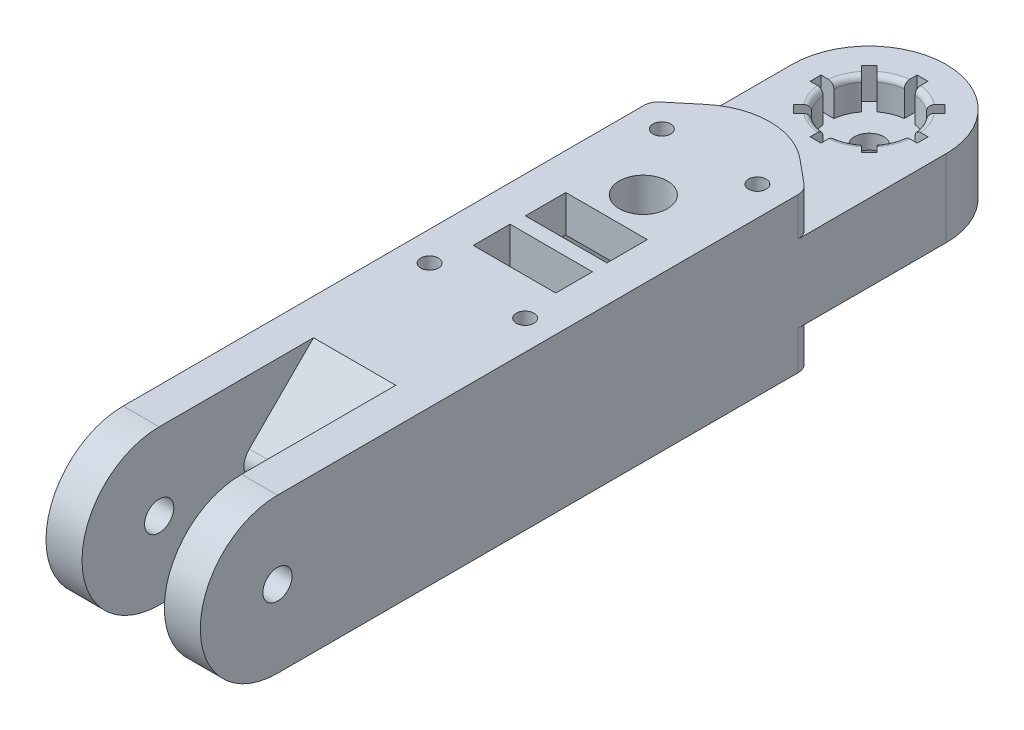
SolidWorks part; units mm, degrees
ref_plane "Front Plane" through (0, 0, 0) normal (0, 0, 1) x (1, 0, 0)
ref_plane "Top Plane" through (0, 0, 0) normal (0, 1, 0) x (1, 0, 0)
ref_plane "Right Plane" through (0, 0, 0) normal (1, 0, 0) x (0, 0, -1)
sketch "Sketch1" plane through (0, 0, 0) normal (0, 0, 1) x (1, 0, 0)
  line L1 (-21, 21) -> (21, 21)
  line L2 (-21, 21) -> (-21, -21)
  line L3 (-21, -21) -> (21, -21)
  line L4 (21, 21) -> (21, -21)
  line L5 (-21, 21) -> (21, -21) construction
  line L6 (-21, -21) -> (21, 21) construction
  point P0 (0, 0)
  dimension "D1" = 42
  dimension "D2" = 42
extrude "Boss-Extrude1" add sketch "Sketch1" along normal blind 140
ref_plane "Plane1" through (0, 0, 140) normal (0, 0, 1) x (1, 0, 0)
sketch "Sketch2" plane through (0, 0, 140) normal (0, 0, 1) x (1, 0, 0)
  line L0 (-21, -21) -> (21, -21) construction
  line L1 (-21, 21) -> (-11.2, 21)
  line L2 (-21, 21) -> (-21, -21)
  line L3 (-21, -21) -> (-11.2, -21)
  line L4 (-11.2, 21) -> (-11.2, -21)
  line L5 (21, 21) -> (-21, 21) construction
  line L6 (21, -21) -> (11.2, -21)
  line L7 (21, -21) -> (21, 21)
  line L8 (21, 21) -> (11.2, 21)
  line L9 (11.2, -21) -> (11.2, 21)
  dimension "D1" = 9.8
  dimension "D2" = 9.8
extrude "Boss-Extrude2" add sketch "Sketch2" along normal blind 21
ref_plane "Plane2" through (-11.2, 0, 0) normal (1, 0, 0) x (0, 0, -1)
sketch "Sketch3" plane through (-11.2, 0, 0) normal (1, 0, 0) x (0, 0, -1)
  line L0 (-161, -21) -> (-161, 21)
  arc A0 (-161, -21) -> (-161, 21) centre (-161, 0) cw
  dimension "D1" = 21
ref_plane "Plane3" through (0, -21, 0) normal (0, -1, 0) x (-1, 0, 0)
ref_plane "Plane4" through (11.2, 0, 0) normal (-1, 0, 0) x (0, 0, 1)
sketch "Sketch5" plane through (11.2, 0, 0) normal (-1, 0, 0) x (0, 0, 1)
  line L0 (161, 21) -> (161, -21)
  line L4 (140, 21) -> (140, -21)
  line L5 (140, -21) -> (161, -21)
  line L6 (161, -21) -> (161, 21)
  line L7 (161, 21) -> (140, 21)
  line L8 (140, 21) -> (140, -21)
  line L9 (140, -21) -> (161, -21)
  line L11 (161, 21) -> (140, 21)
  arc A0 (161, 21) -> (161, -21) centre (161, 0) cw
  dimension "D1" = 21
  dimension "D2" = 0
extrude "Boss-Extrude4" add sketch "Sketch5" against normal blind 9.8 contours A0 L0 region at (11.2, 0, 169.9127)
extrude "Boss-Extrude5" add sketch "Sketch3" against normal blind 9.8
sketch "Sketch6" plane through (11.2, 0, 0) normal (-1, 0, 0) x (0, 0, 1)
  line L0 (161, -21) -> (161, 21) construction
  circle A0 centre (161, 0) radius 3.975
  dimension "D1" = 7.95
extrude "Cut-Extrude1" cut sketch "Sketch6" against normal through all
ref_plane "Plane5" through (-11.2, 0, 0) normal (1, 0, 0) x (0, 0, -1)
sketch "Sketch8" plane through (-11.2, 0, 0) normal (1, 0, 0) x (0, 0, -1)
  line L0 (-161, -21) -> (-161, 21) construction
  circle A0 centre (-161, 0) radius 3.975
  dimension "D1" = 7.95
extrude "Cut-Extrude2" cut sketch "Sketch8" against normal through all
ref_plane "Plane6" through (0, 0, 0) normal (0, 0, -1) x (-1, 0, 0)
sketch "Sketch9" plane through (0, 0, 0) normal (0, 0, -1) x (-1, 0, 0)
  line L0 (21, 21) -> (21, -21) construction
  line L1 (21, 10.5) -> (-21, 10.5)
  line L2 (21, 10.5) -> (21, -10.5)
  line L3 (21, -10.5) -> (-21, -10.5)
  line L4 (-21, 10.5) -> (-21, -10.5)
  line L5 (-21, -21) -> (-21, 21) construction
  line L6 (-21, 21) -> (21, 21) construction
  line L7 (21, -21) -> (-21, -21) construction
  dimension "D1" = 10.5
  dimension "D2" = 10.5
extrude "Boss-Extrude6" add sketch "Sketch9" along normal blind 21
ref_plane "Plane7" through (0, -10.5, 0) normal (0, -1, 0) x (-1, 0, 0)
sketch "Sketch10" plane through (0, -10.5, 0) normal (0, -1, 0) x (-1, 0, 0)
  line L0 (-21, 21) -> (21, 21)
  arc A0 (-21, 21) -> (21, 21) centre (0, 21) cw
  dimension "D1" = 21
extrude "Boss-Extrude7" add sketch "Sketch10" against normal blind 21
sketch "Sketch11" plane through (0, -10.5, 0) normal (0, -1, 0) x (-1, 0, 0)
  line L0 (21, 21) -> (-21, 21) construction
  circle A0 centre (0, 21) radius 11.35
  dimension "D1" = 22.7
extrude "Cut-Extrude3" cut sketch "Sketch11" against normal blind 8.5
ref_plane "Plane8" through (11.2, 0, 0) normal (-1, 0, 0) x (0, 0, 1)
sketch "Sketch16" plane through (11.2, 0, 0) normal (-1, 0, 0) x (0, 0, 1)
  line L0 (140, 21) -> (140, 0)
  line L1 (140, 21) -> (140, -21) construction
  line L2 (140, 0) -> (140, -21)
  line L3 (140, -21) -> (119, -21)
  line L4 (119, -21) -> (140, 0)
  line L5 (140, 21) -> (119, 21)
  line L6 (119, 21) -> (140, 0)
  line L7 (161, 0) -> (140, 0) construction
  dimension "D1" = 21
  dimension "D2" = 21
extrude "Cut-Extrude4" cut sketch "Sketch16" along normal blind 22.4 contours L0 L5 L6 | L2 L3 L4
fillet "Fillet1" radius 5 1 edges at (0, 0, 140)
ref_plane "Plane9" through (0, -10.5, 0) normal (0, -1, 0) x (-1, 0, 0)
ref_plane "Plane10" through (0, 10.5, 0) normal (0, 1, 0) x (1, 0, 0)
sketch "Sketch18" plane through (0, 10.5, 0) normal (0, 1, 0) x (1, 0, 0)
  line L0 (21, 21) -> (-21, 21) construction
  circle A0 centre (0, 21) radius 11.1605
  dimension "D1" = 22.321
extrude "Cut-Extrude5" cut sketch "Sketch18" against normal blind 8.5
sketch "Sketch19" plane through (0, -2, 0) normal (0, -1, 0) x (1, 0, 0)
  circle A0 centre (0, -21) radius 3.975
  dimension "D1" = 7.95
extrude "Cut-Extrude6" cut sketch "Sketch19" against normal blind 8.5
fillet "Fillet4" radius 1.5 1 edges at (11.35, -10.5, -21)
fillet "Fillet5" radius 1.5 1 edges at (-11.1605, 10.5, -21)
sketch "Sketch20" plane through (0, 10.5, 0) normal (0, 1, 0) x (1, 0, 0)
  line L1 (-1.48, 35.5655) -> (1.48, 35.5655)
  line L2 (-1.48, 35.5655) -> (-1.48, 31.7555)
  line L3 (-1.48, 31.7555) -> (1.48, 31.7555)
  line L4 (1.48, 35.5655) -> (1.48, 31.7555)
  line L5 (-1.48, 35.5655) -> (1.48, 31.7555) construction
  line L6 (-1.48, 31.7555) -> (1.48, 35.5655) construction
  circle A0 centre (0, 21) radius 12.6605 construction
  point P0 (0, 33.6605)
  dimension "D1" = 2.96
  dimension "D2" = 3.81
extrude "Cut-Extrude7" cut sketch "Sketch20" against normal blind 8.5
pattern_circular "CirPattern1" count 8 over 360 about axis through (0, 2, -21) along (0, 1, 0) of "Cut-Extrude7"
ref_plane "Plane11" through (0, 0, 0) normal (0, 1, 0) x (1, 0, 0)
mirror "Mirror1" about plane through (0, 0, 0) normal (0, 1, 0) of "CirPattern1"
sketch "Sketch25" plane through (0, -21, 0) normal (0, -1, 0) x (1, 0, 0)
  line L0 (0, 0) -> (0, 119) construction
  line L2 (-21, 0) -> (21, 0) construction
  line L3 (17, 78.5) -> (-17, 78.5)
  line L4 (17, 78.5) -> (17, 29.5)
  line L5 (17, 29.5) -> (-17, 29.5)
  line L6 (-17, 78.5) -> (-17, 29.5)
  line L7 (17, 78.5) -> (-17, 29.5) construction
  line L8 (17, 29.5) -> (-17, 78.5) construction
  point P5 (0, 54)
  dimension "D1" = 34
  dimension "D2" = 49
  dimension "D3" = 54
extrude "Cut-Extrude11" cut sketch "Sketch25" against normal blind 32 contours L3 L6 L5 L4 region at (0, -21, 54)
sketch "Sketch26" plane through (0, -21, 0) normal (0, -1, 0) x (1, 0, 0)
  line L0 (0, 29.5) -> (0, 18.4) construction
  line L1 (17, 29.5) -> (-17, 29.5)
  line L2 (17, 29.5) -> (17, 26.5)
  line L3 (17, 26.5) -> (-17, 26.5)
  line L4 (-17, 29.5) -> (-17, 26.5)
  line L5 (-17, 26.5) -> (17, 26.5)
  line L6 (-17, 26.5) -> (-17, 18.4)
  line L7 (-17, 18.4) -> (17, 18.4)
  line L8 (17, 26.5) -> (17, 18.4)
  line M6 (17, 29.5) -> (-17, 29.5)
  line M7 (-21, 0) -> (21, 0)
  dimension "D1" = 3
  dimension "D2" = 8.1
extrude "Cut-Extrude12" cut sketch "Sketch26" against normal blind 27 contours L3 L0 L8 M7 | L0 L3 L2 M6 | L0 L1 L4 L5 | L0 L5 L6 M7 | L0 L6 L7 M7 | L0 L7 L8 M7 region at (8.5, -21, 28) region at (-8.5, -21, 28) region at (8.5, -21, 22.45) region at (-8.5, -21, 22.45)
sketch "Sketch30" plane through (0, 6, 0) normal (0, -1, 0) x (1, 0, 0)
  line L0 (0, 29.5) -> (0, 18.4) construction
  line L1 (17, 29.5) -> (-17, 29.5) construction
  line L2 (-17, 18.4) -> (17, 18.4) construction
  line L3 (-17, 29.5) -> (-17, 18.4) construction
  circle A0 centre (-13, 22.4) radius 4
  circle A1 centre (-13, 22.4) radius 2.4
  dimension "D1" = 8
  dimension "D2" = 4.8
extrude "Cut-Extrude13" cut sketch "Sketch30" against normal through all contours A1 region at (-13, 6, 22.4)
ref_plane "Plane12" through (0, 0, 0) normal (-1, 0, 0) x (0, 0, 1)
mirror "Mirror9" about plane through (0, 0, 0) normal (-1, 0, 0) of "Cut-Extrude13"
ref_plane "Plane13" through (0, 0, 54) normal (0, 0, 1) x (1, 0, 0)
sketch "Sketch32" plane through (0, 21, 0) normal (0, 1, 0) x (1, 0, 0)
  line L3 (0, 0) -> (0, -65.7087) construction
  line L4 (0, 17.6) -> (0, -17.6) construction
  line L10 (0, 0) -> (21, -17.4215)
  line L11 (21, -161) -> (21, 0) construction
  line L13 (-21, -161) -> (-21, 0) construction
  line L14 (-21, -17.4215) -> (0, 0)
  line L15 (0, 0) -> (-21, 0)
  line L16 (-21, 0) -> (-21, -17.4215)
  line L17 (0, 0) -> (21, 0)
  line L18 (21, 0) -> (21, -17.4215)
  line M13 (21, -161) -> (21, 0)
  line M14 (21, 0) -> (-21, 0)
  line M15 (-21, 0) -> (-21, -161)
fillet "Fillet10" radius 3 2 edges at (-17, -7.5, 18.4) (17, -7.5, 18.4)
ref_plane "Plane14" through (0, 0, 54) normal (0, 0, -1) x (-1, 0, 0)
mirror "Mirror12" about plane through (0, 0, 54) normal (0, 0, -1) of "Fillet10", "Mirror9", "Cut-Extrude13", "Cut-Extrude12"
extrude "Cut-Extrude16" cut sketch "Sketch32" against normal blind 10.5 contours L14 M15 M14 | L10 M14 M13 region at (14, 21, 5.8072) region at (-14, 21, 5.8072)
fillet "Fillet12" radius 20 1 edges at (0, 15.75, 0)
mirror "Mirror13" about plane through (0, 0, 0) normal (0, 1, 0) of "Fillet12", "Cut-Extrude16"
fillet "Fillet13" radius 4 4 edges at (-21, 15.75, 17.4215) (-21, -15.75, 17.4215) (21, -15.75, 17.4215) (21, 15.75, 17.4215)
sketch "Sketch33" plane through (0, 11, 0) normal (0, -1, 0) x (1, 0, 0)
  line L0 (-17, 78.5) -> (-17, 65.5) construction
  line L1 (-17, 78.5) -> (-17, 29.5) construction
  line L2 (0, 78.5) -> (0, 29.5) construction
  line L3 (17, 78.5) -> (-17, 78.5) construction
  line L4 (17, 29.5) -> (-17, 29.5) construction
  line L5 (-17, 65.5) -> (17, 65.5) construction
  line L7 (17, 86.6) -> (17, 21.4) construction
  line L8 (-11.225, 65.5) -> (11.225, 65.5)
  line L9 (-11.225, 65.5) -> (-11.225, 75.5)
  line L10 (-11.225, 75.5) -> (11.225, 75.5)
  line L11 (11.225, 75.5) -> (11.225, 65.5)
  line L12 (-17, 47) -> (17, 47) construction
  line L13 (17, 78.5) -> (17, 29.5) construction
  line L15 (11.1, 50.44) -> (-11.1, 50.44)
  line L16 (11.1, 50.44) -> (11.1, 61.44)
  line L17 (11.1, 61.44) -> (-11.1, 61.44)
  line L18 (-11.1, 50.44) -> (-11.1, 61.44)
  circle A0 centre (0, 40.44) radius 6.56
  point P12 (0, 29.5)
  point P17 (0, 65.5)
  point P26 (0, 50.44)
  dimension "D5" = 13.12
  dimension "D1" = 13
  dimension "D2" = 22.45
  dimension "D3" = 10
  dimension "D4" = 17.5
  dimension "D6" = 21
  dimension "D7" = 22.2
  dimension "D8" = 11
extrude "Cut-Extrude17" cut sketch "Sketch33" against normal through all
